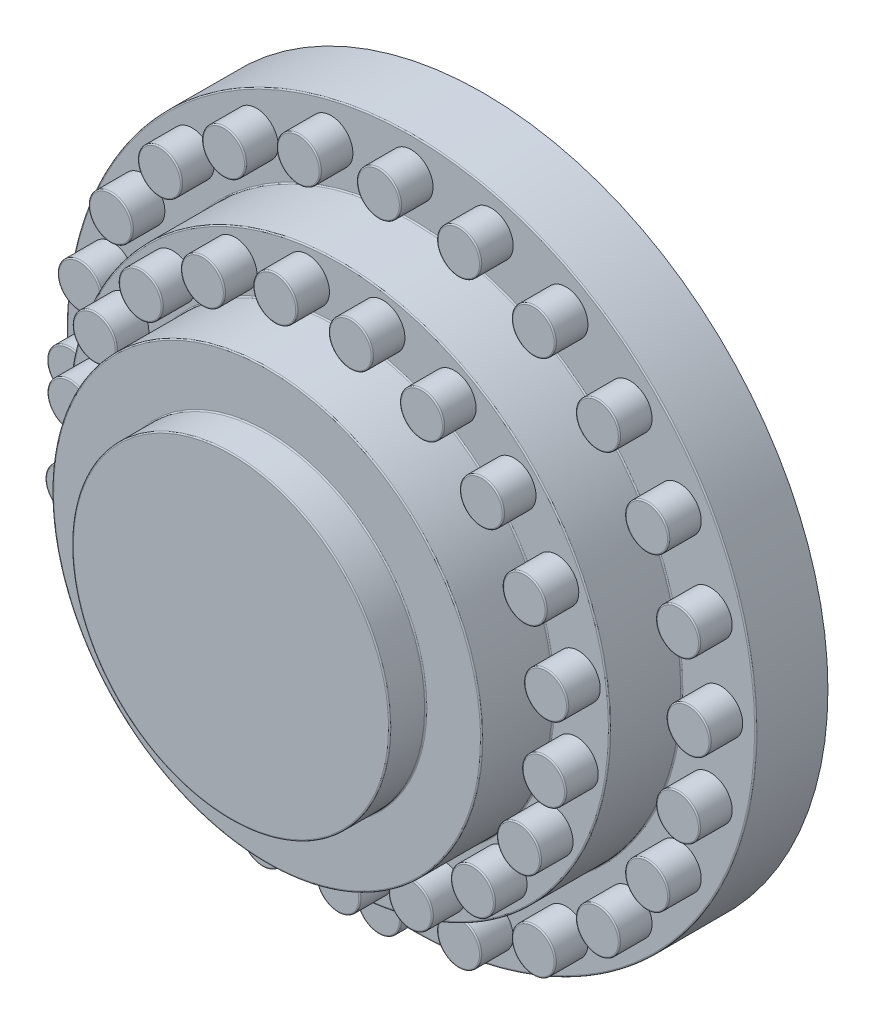
SolidWorks part; units mm, degrees
ref_plane "Front Plane" through (0, 0, 0) normal (0, 0, 1) x (1, 0, 0)
ref_plane "Top Plane" through (0, 0, 0) normal (0, 1, 0) x (1, 0, 0)
ref_plane "Right Plane" through (0, 0, 0) normal (1, 0, 0) x (0, 0, -1)
sketch "Sketch1" plane through (0, 0, 0) normal (0, 0, 1) x (1, 0, 0)
  circle A0 centre (0, 0) radius 296.25
  dimension "D1" = 592.5
extrude "Boss-Extrude1" add sketch "Sketch1" along normal blind 62
sketch "Sketch2" plane through (0, 0, 62) normal (0, 0, 1) x (1, 0, 0)
  circle A0 centre (0, 0) radius 232.5
  dimension "D1" = 465
extrude "Boss-Extrude2" add sketch "Sketch2" along normal blind 62
sketch "Sketch3" plane through (0, 0, 124) normal (0, 0, 1) x (1, 0, 0)
  circle A0 centre (0, 0) radius 184.5
  dimension "D1" = 369
extrude "Boss-Extrude3" add sketch "Sketch3" along normal blind 62
sketch "Sketch4" plane through (0, 0, 186) normal (0, 0, 1) x (1, 0, 0)
  circle A0 centre (0, 0) radius 136.5
  dimension "D1" = 273
extrude "Boss-Extrude4" add sketch "Sketch4" along normal blind 31
sketch "Sketch5" plane through (0, 0, 62) normal (0, 0, 1) x (1, 0, 0)
  circle A1 centre (-266.25, 0) radius 18.75
  circle A2 centre (0, 0) radius 266.25
  circle A3 centre (0, 0) radius 266.25 construction
  dimension "D2" = 37.5
  dimension "D1" = 30
extrude "Boss-Extrude5" add sketch "Sketch5" along normal blind 28
fillet "Fillet1" radius 1 8 edges at (232.5, 0, 62) (232.5, 0, 124) (184.5, 0, 124) (184.5, 0, 186) (136.5, 0, 186) (136.5, 0, 217) (296.25, 0, 62) (-247.5, 0, 90) conic rho 0.5
sketch "Sketch7" plane through (0, 0, 124) normal (0, 0, 1) x (1, 0, 0)
  line L0 (-266.25, 0) -> (0, 0) construction
  line L1 (0, 0) -> (-205.7248, -27.0842) construction
  circle A1 centre (-205.7248, -27.0842) radius 18.75
  circle A2 centre (0, 0) radius 207.5
  circle A3 centre (0, 0) radius 207.5 construction
  dimension "D2" = 37.5
  dimension "D3" = 7.5
  dimension "D1" = 25
extrude "Boss-Extrude6" add sketch "Sketch7" along normal blind 28
sketch "Sketch8" plane through (0, 0, 0) normal (0, 0, -1) x (-1, 0, 0)
  circle A0 centre (0, 0) radius 57.5
  dimension "D1" = 115
extrude "Cut-Extrude1" cut sketch "Sketch8" against normal blind 28
fillet "Fillet2" radius 1 1 edges at (-186.9748, -27.0842, 152) conic rho 0.5
pattern_circular "CirPattern1" count 24 over 360 about axis through (0, 0, 186) along (0, 0, -1) of "Boss-Extrude5", "Fillet1"
pattern_circular "CirPattern2" count 20 over 360 about axis through (0, 0, 186) along (0, 0, -1) of "Boss-Extrude6", "Fillet2" reverse direction yes
